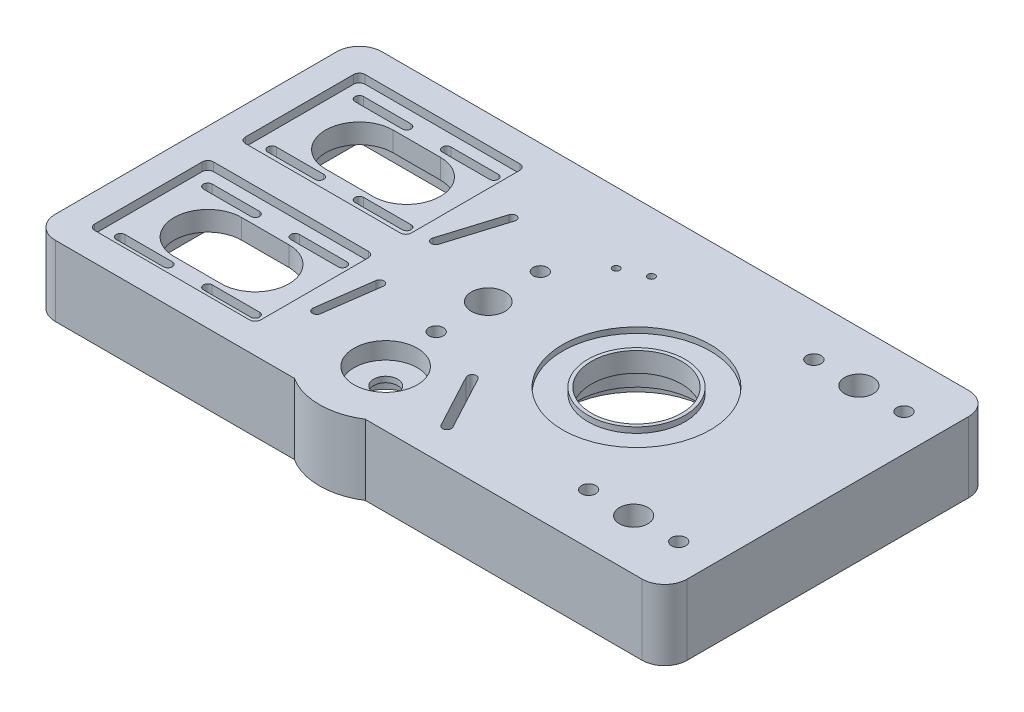
SolidWorks part; units mm, degrees
ref_plane "Front Plane" through (0, 0, 0) normal (0, 0, 1) x (1, 0, 0)
ref_plane "Top Plane" through (0, 0, 0) normal (0, 1, 0) x (1, 0, 0)
ref_plane "Right Plane" through (0, 0, 0) normal (1, 0, 0) x (0, 0, -1)
sketch "Sketch1" plane through (0, 0, 0) normal (0, 1, 0) x (1, 0, 0)
  line L1 (-113.431, 55) -> (95, 55)
  line L2 (-118.431, 50) -> (-118.431, -50)
  line L3 (-113.431, -55) -> (95, -55)
  line L4 (100, 50) -> (100, -50)
  arc A0 (95, 55) -> (100, 50) centre (95, 50) cw
  arc A1 (95, -55) -> (100, -50) centre (95, -50) ccw
  arc A2 (-118.431, -50) -> (-113.431, -55) centre (-113.431, -50) ccw
  arc A3 (-118.431, 50) -> (-113.431, 55) centre (-113.431, 50) cw
  point P0 (0, 0)
  point P18 (0, 0)
  dimension "D3" = 5
  dimension "D1" = 208.431
  dimension "D2" = 110
extrude "Boss-Extrude1" add sketch "Sketch1" along normal blind 10
sketch "Sketch6" plane through (0, 0, 0) normal (0, -1, 0) x (1, 0, 0)
  line L0 (0, 0) -> (35, 0) construction
  circle A0 centre (35, 0) radius 30
  dimension "D2" = 60
  dimension "D1" = 35
extrude "Boss-Extrude3" add sketch "Sketch6" along normal blind 10
sketch "Sketch8" plane through (0, 0, 0) normal (0, 0, 1) x (1, 0, 0)
  line L0 (5, -10) -> (-5, 0)
  line L1 (-5, 0) -> (5, 0)
  line L2 (5, 0) -> (5, -10)
  dimension "D1" = 45
sketch "Sketch9" plane through (0, -10, 0) normal (0, -1, 0) x (1, 0, 0)
  arc A0 (5.1043, 2.5) -> (5.1043, -2.5) centre (35, 0) ccw
  circle A1 centre (35, 0) radius 30 construction
  point P6 (5, 0)
  dimension "D1" = 5
sketch "Sketch10" plane through (0, 0, 0) normal (0, -1, 0) x (1, 0, 0)
  line L0 (-5, -2.5) -> (-5, 2.5)
  line L1 (5, 0) -> (-5, 0) construction
  arc A0 (5.1043, 2.5) -> (5.1043, -2.5) centre (35, 0) ccw construction
  arc A1 (5.1043, 2.5) -> (5.1043, -2.5) centre (35, 0) ccw
  point P4 (-5, 0)
  dimension "D1" = 5
ref_axis "Axis2" through (35, -10, 0) along (0, 1, 0)
ref_plane "Plane1" through (35, 0, 0) normal (1, 0, 0) x (0, 0, -1)
sketch "Sketch40" plane through (0, -10, 0) normal (0, -1, 0) x (1, 0, 0)
  circle A0 centre (35, 0) radius 26.25
  dimension "D1" = 52.5
extrude "Cut-Extrude1" cut sketch "Sketch40" against normal blind 5
sketch "Sketch42" plane through (0, -5, 0) normal (0, -1, 0) x (1, 0, 0)
  circle A0 centre (35, 0) radius 21.25
  dimension "D1" = 42.5
extrude "Cut-Extrude2" cut sketch "Sketch42" against normal blind 8
sketch "Sketch43" plane through (0, 3, 0) normal (0, -1, 0) x (1, 0, 0)
  circle A0 centre (35, 0) radius 16
  dimension "D1" = 32
extrude "Cut-Extrude3" cut sketch "Sketch43" against normal through all
sketch "Sketch44" plane through (0, 10, 0) normal (0, 1, 0) x (1, 0, 0)
  circle A0 centre (35, 0) radius 17.25
  circle A1 centre (35, 0) radius 26.25
  dimension "D1" = 34.5
  dimension "D2" = 52.5
extrude "Cut-Extrude4" cut sketch "Sketch44" against normal blind 2
sketch "Sketch45" plane through (0, 10, 0) normal (0, 1, 0) x (1, 0, 0)
  line L0 (95, 55) -> (-113.431, 55) construction
  line L5 (-109.431, 48) -> (-54.431, 48)
  line L6 (-111.431, 46) -> (-111.431, 7.5)
  line L7 (-109.431, 5.5) -> (-54.431, 5.5)
  line L8 (-52.431, 46) -> (-52.431, 7.5)
  line L9 (-109.431, -5.8) -> (-54.431, -5.8)
  line L10 (-111.431, -7.8) -> (-111.431, -46)
  line L11 (-109.431, -48) -> (-54.431, -48)
  line L12 (-52.431, -7.8) -> (-52.431, -46)
  line L13 (-118.431, 50) -> (-118.431, -50) construction
  line L14 (-113.431, -55) -> (95, -55) construction
  line L15 (100, -50) -> (100, 50) construction
  arc A0 (-111.431, -46) -> (-109.431, -48) centre (-109.431, -46) ccw
  arc A1 (-54.431, -48) -> (-52.431, -46) centre (-54.431, -46) ccw
  arc A2 (-54.431, -5.8) -> (-52.431, -7.8) centre (-54.431, -7.8) cw
  arc A3 (-111.431, -7.8) -> (-109.431, -5.8) centre (-109.431, -7.8) cw
  arc A4 (-109.431, 48) -> (-111.431, 46) centre (-109.431, 46) ccw
  arc A5 (-111.431, 7.5) -> (-109.431, 5.5) centre (-109.431, 7.5) ccw
  arc A6 (-54.431, 5.5) -> (-52.431, 7.5) centre (-54.431, 7.5) ccw
  arc A7 (-54.431, 48) -> (-52.431, 46) centre (-54.431, 46) cw
  point P16 (-111.431, -48)
  point P21 (-52.431, -5.8)
  point P24 (-111.431, -5.8)
  point P27 (-111.431, 48)
  point P30 (-111.431, 5.5)
  point P35 (-52.431, 48)
  dimension "D9" = 2
  dimension "D10" = 2
  dimension "D2" = 42.5
  dimension "D3" = 152.431
  dimension "D4" = 42.2
  dimension "D5" = 7
  dimension "D6" = 7
  dimension "D7" = 7
  dimension "D8" = 7
  dimension "D11" = 152.431
extrude "Cut-Extrude5" cut sketch "Sketch45" against normal blind 3
sketch "Sketch47" plane through (0, 7, 0) normal (0, 1, 0) x (1, 0, 0)
  line L1 (-111.431, -7.8) -> (-111.431, -46) construction
  line L2 (-90.331, -26.9) -> (-73.531, -26.9) construction
  line L5 (-105.831, -11.4) -> (-89.031, -11.4) construction
  line L6 (-90.331, -14.9) -> (-73.531, -14.9)
  line L7 (-73.531, -38.9) -> (-90.331, -38.9)
  line L8 (-52.431, -46) -> (-52.431, -7.8) construction
  line L10 (-105.831, -11.4) -> (-74.831, -11.4) construction
  line L11 (-105.831, -11.4) -> (-105.831, -42.4) construction
  line L12 (-105.831, -42.4) -> (-74.831, -42.4) construction
  line L13 (-74.831, -11.4) -> (-74.831, -42.4) construction
  line L14 (-105.831, -11.4) -> (-74.831, -42.4) construction
  line L15 (-105.831, -42.4) -> (-74.831, -11.4) construction
  line L16 (-89.031, -11.4) -> (-58.031, -11.4) construction
  line L17 (-89.031, -11.4) -> (-89.031, -42.4) construction
  line L18 (-89.031, -42.4) -> (-58.031, -42.4) construction
  line L19 (-58.031, -11.4) -> (-58.031, -42.4) construction
  line L20 (-89.031, -11.4) -> (-58.031, -42.4) construction
  line L21 (-89.031, -42.4) -> (-58.031, -11.4) construction
  line L27 (-105.831, -9.85) -> (-89.031, -9.85)
  line L29 (-105.831, -12.95) -> (-89.031, -12.95)
  line L30 (-58.031, -11.4) -> (-74.831, -11.4) construction
  line L31 (-58.031, -12.95) -> (-74.831, -12.95)
  line L32 (-58.031, -9.85) -> (-74.831, -9.85)
  line L33 (-105.831, -42.4) -> (-89.031, -42.4) construction
  line L34 (-105.831, -40.85) -> (-89.031, -40.85)
  line L35 (-105.831, -43.95) -> (-89.031, -43.95)
  line L36 (-58.031, -42.4) -> (-74.831, -42.4) construction
  line L37 (-58.031, -43.95) -> (-74.831, -43.95)
  line L38 (-58.031, -40.85) -> (-74.831, -40.85)
  arc A1 (-73.531, -38.9) -> (-73.531, -14.9) centre (-73.531, -26.9) ccw
  arc A2 (-90.331, -14.9) -> (-90.331, -38.9) centre (-90.331, -26.9) ccw
  arc A15 (-105.831, -9.85) -> (-105.831, -12.95) centre (-105.831, -11.4) ccw
  arc A16 (-89.031, -12.95) -> (-89.031, -9.85) centre (-89.031, -11.4) ccw
  arc A17 (-58.031, -12.95) -> (-58.031, -9.85) centre (-58.031, -11.4) ccw
  arc A18 (-74.831, -9.85) -> (-74.831, -12.95) centre (-74.831, -11.4) ccw
  arc A19 (-105.831, -40.85) -> (-105.831, -43.95) centre (-105.831, -42.4) ccw
  arc A20 (-89.031, -43.95) -> (-89.031, -40.85) centre (-89.031, -42.4) ccw
  arc A21 (-58.031, -43.95) -> (-58.031, -40.85) centre (-58.031, -42.4) ccw
  arc A22 (-74.831, -40.85) -> (-74.831, -43.95) centre (-74.831, -42.4) ccw
  point P12 (-97.431, -11.4)
  point P23 (-66.431, -11.4)
  point P28 (-97.431, -42.4)
  point P33 (-66.431, -42.4)
  dimension "D1" = 21.1
  dimension "D2" = 24
  dimension "D4" = 24
  dimension "D5" = 31
  dimension "D7" = 3.1
  dimension "D8" = 3.1
  dimension "D9" = 3.1
  dimension "D10" = 3.1
  dimension "D3" = 21.1
  dimension "D6" = 31
  dimension "D11" = 31
  dimension "D12" = 31
extrude "Cut-Extrude6" cut sketch "Sketch47" against normal through all
sketch "Sketch48" plane through (0, 7, 0) normal (0, 1, 0) x (1, 0, 0)
  line L0 (-54.431, 48) -> (-109.431, 48) construction
  line L1 (-111.431, 46) -> (-111.431, 7.5) construction
  circle A0 centre (-81.931, 26.75) radius 3.5
  point P4 (-81.931, 48)
  point P7 (-111.431, 26.75)
  dimension "D1" = 7
extrude "Cut-Extrude7" cut sketch "Sketch48" against normal through all
sketch "Sketch49" plane through (0, 10, 0) normal (0, 1, 0) x (1, 0, 0)
  circle A0 centre (-15.9285, -38.1594) radius 11.25
extrude "Cut-Extrude8" cut sketch "Sketch49" against normal blind 6
sketch "Sketch50" plane through (0, 4, 0) normal (0, 1, 0) x (1, 0, 0)
  circle A0 centre (-15.9285, -38.1594) radius 4.25
  dimension "D1" = 8.5
extrude "Cut-Extrude9" cut sketch "Sketch50" against normal through all
sketch "Sketch51" plane through (0, 0, 0) normal (0, -1, 0) x (1, 0, 0)
  circle A0 centre (-15.9285, 38.1594) radius 11.25
  dimension "D1" = 22.5
extrude "Cut-Extrude10" cut sketch "Sketch51" against normal blind 2
sketch "Sketch56" plane through (0, 10, 0) normal (0, 1, 0) x (1, 0, 0)
  line L0 (90, 40) -> (58, 40) construction
  line L1 (95, 55) -> (-113.431, 55) construction
  line L2 (100, -50) -> (100, 50) construction
  circle A0 centre (74, 40) radius 5.05
  circle A1 centre (58, 40) radius 2.55
  circle A2 centre (90, 40) radius 2.55
  point P5 (74, 40)
  dimension "D1" = 10.1
  dimension "D3" = 5.1
  dimension "D4" = 5.1
  dimension "D2" = 32
  dimension "D5" = 15
  dimension "D6" = 10
extrude "Cut-Extrude13" cut sketch "Sketch56" against normal through all
ref_axis "Axis4" through (74, 0, -40) along (0, 1, 0)
sketch "Sketch54" plane through (0, 10, 0) normal (0, 1, 0) x (1, 0, 0)
  line L0 (-17.6515, -18.5) -> (-17.6515, 18.5) construction
  circle A0 centre (-17.6515, 0) radius 6
  circle A1 centre (-17.6515, 18.5) radius 2.55
  circle A2 centre (-17.6515, -18.5) radius 2.55
  point P5 (-17.6515, 0)
  point P6 (-17.6515, 0)
  dimension "D1" = 12
  dimension "D3" = 5.1
  dimension "D4" = 5.1
  dimension "D2" = 37
  dimension "D5" = 100
extrude "Cut-Extrude12" cut sketch "Sketch54" against normal blind 10
sketch "Sketch55" plane through (0, 10, 0) normal (0, 1, 0) x (1, 0, 0)
  line L0 (90, -40) -> (58, -40) construction
  line L1 (-113.431, -55) -> (95, -55) construction
  line L2 (100, -50) -> (100, 50) construction
  circle A0 centre (74, -40) radius 5.05
  circle A1 centre (58, -40) radius 2.55
  circle A2 centre (90, -40) radius 2.55
  point P5 (74, -40)
  dimension "D1" = 10.1
  dimension "D3" = 5.1
  dimension "D4" = 5.1
  dimension "D2" = 32
  dimension "D5" = 15
  dimension "D6" = 10
extrude "Cut-Extrude14" cut sketch "Sketch55" against normal through all
sketch "Sketch61" plane through (0, 0, 0) normal (0, -1, 0) x (1, 0, 0)
  line L1 (-22.3211, 18.7547) -> (-20.2069, 14.5834)
  line L2 (-20.2069, 14.5834) -> (-15.5373, 14.3286)
  line L3 (-15.5373, 14.3286) -> (-12.9819, 18.2453)
  line L4 (-12.9819, 18.2453) -> (-15.0961, 22.4166)
  line L5 (-15.0961, 22.4166) -> (-19.7657, 22.6714)
  line L6 (-19.7657, 22.6714) -> (-22.3211, 18.7547)
  line L7 (-19.8779, -22.6126) -> (-15.2031, -22.4844)
  line L8 (-15.2031, -22.4844) -> (-12.9767, -18.3718)
  line L9 (-12.9767, -18.3718) -> (-15.4252, -14.3874)
  line L10 (-15.4252, -14.3874) -> (-20.0999, -14.5156)
  line L11 (-20.0999, -14.5156) -> (-22.3263, -18.6282)
  line L12 (-22.3263, -18.6282) -> (-19.8779, -22.6126)
  circle A0 centre (-17.6515, 18.5) radius 4.05 construction
  circle A1 centre (-17.6515, -18.5) radius 4.05 construction
  dimension "D1" = 8.1
  dimension "D2" = 8.1
extrude "Cut-Extrude17" cut sketch "Sketch61" against normal blind 3
ref_axis "Axis5" through (74, 0, 40) along (0, 1, 0)
ref_axis "Axis6" through (-17.6515, 0, 0) along (0, 1, 0)
sketch "Sketch66" plane through (0, 0, 0) normal (0, -1, 0) x (1, 0, 0)
  line L4 (-26.2904, 51) -> (-113.431, 51)
  line L8 (-113.431, -51) -> (95, -51)
  line L9 (96, -50) -> (96, 50)
  line L10 (95, 51) -> (-113.431, 51)
  line L11 (-114.431, 50) -> (-114.431, -50)
  line L12 (-113.431, -51) -> (95, -51)
  line L13 (96, -50) -> (96, 50)
  line L14 (95, 51) -> (-5.5666, 51)
  line L15 (-114.431, 50) -> (-114.431, -50)
  arc A4 (-5.5666, 51) -> (-26.2904, 51) centre (-15.9285, 38.1594) ccw
  arc A8 (95, -51) -> (96, -50) centre (95, -50) ccw
  arc A9 (96, 50) -> (95, 51) centre (95, 50) ccw
  arc A10 (-113.431, 51) -> (-114.431, 50) centre (-113.431, 50) ccw
  arc A11 (-114.431, -50) -> (-113.431, -51) centre (-113.431, -50) ccw
  arc A12 (95, -51) -> (96, -50) centre (95, -50) ccw
  arc A13 (96, 50) -> (95, 51) centre (95, 50) ccw
  arc A14 (-113.431, 51) -> (-114.431, 50) centre (-113.431, 50) ccw
  arc A15 (-114.431, -50) -> (-113.431, -51) centre (-113.431, -50) ccw
  dimension "D2" = 33
  dimension "D1" = 4
extrude "Extrude-Thin4" add sketch "Sketch66" along normal blind 15 and the other way blind 10 thin thin type one direction wall 7
fillet "Fillet2" radius 20 2 edges at (-5.5666, -7.5, 51) (-26.2904, -7.5, 51)
sketch "Sketch70" plane through (0, 0, 0) normal (0, 0, 1) x (1, 0, 0)
  line L0 (62.8394, -8.3805) -> (96.3572, -8.3805)
rib "Rib4" sketch "Sketch70" sketch "Sketch70" thickness 5 extrusion direction parallel to sketch draft on no parameters "D1"=5
ref_axis "Axis7" through (35, 10, 0) along (0, -1, 0)
ref_plane "Plane2" through (35, 0, 0) normal (1, 0, 0) x (0, 0, -1)
sketch "Sketch71" plane through (35, 0, 0) normal (1, 0, 0) x (0, 0, -1)
  line L0 (27.6002, -9.821) -> (51.9246, -9.821)
rib "Rib5" sketch "Sketch71" sketch "Sketch71" thickness 5 extrusion direction parallel to sketch draft on no parameters "D1"=5
sketch "Sketch72" plane through (35, 0, 0) normal (1, 0, 0) x (0, 0, -1)
  line L0 (-28.0959, -9.864) -> (-52.7518, -9.864)
rib "Rib6" sketch "Sketch72" sketch "Sketch72" thickness 5 extrusion direction parallel to sketch draft on no parameters "D1"=5
sketch "Sketch73" plane through (0, 10, 0) normal (0, 1, 0) x (1, 0, 0)
  circle A0 centre (3.5607, 36.7397) radius 1.25
  circle A1 centre (-5.1555, 32.9611) radius 1.25
extrude "Cut-Extrude18" cut sketch "Sketch73" against normal up to next
sketch "Sketch77" plane through (0, 0, 0) normal (0, -1, 0) x (1, 0, 0)
  line L0 (13.3067, 45.6331) -> (2.9884, 26.3868) construction
  line L1 (14.6728, 44.9007) -> (4.3545, 25.6545)
  line L2 (11.9406, 46.3654) -> (1.6224, 27.1192)
  arc A0 (14.6728, 44.9007) -> (11.9406, 46.3654) centre (13.3067, 45.6331) ccw
  arc A1 (1.6224, 27.1192) -> (4.3545, 25.6545) centre (2.9884, 26.3868) ccw
  point P2 (8.1476, 36.0099)
extrude "Cut-Extrude19" cut sketch "Sketch77" against normal up to next
sketch "Sketch80" plane through (0, 0, 0) normal (0, -1, 0) x (1, 0, 0)
  line L0 (-42.565, 13.7036) -> (-45.2535, 33.2752) construction
  line L1 (-44.1005, 13.4927) -> (-46.7891, 33.0642)
  line L2 (-41.0294, 13.9146) -> (-43.7179, 33.4861)
  arc A0 (-44.1005, 13.4927) -> (-41.0294, 13.9146) centre (-42.565, 13.7036) ccw
  arc A1 (-43.7179, 33.4861) -> (-46.7891, 33.0642) centre (-45.2535, 33.2752) ccw
  point P2 (-43.9092, 23.4894)
extrude "Cut-Extrude20" cut sketch "Sketch80" against normal up to next
mirror "Mirror2" about plane through (0, 0, 0) normal (0, 0, 1) of "Cut-Extrude6"
sketch "Sketch81" plane through (0, 0, 0) normal (0, -1, 0) x (1, 0, 0)
  line L0 (-39.2418, -29.9538) -> (-45.5961, -9.29) construction
  line L1 (-40.7233, -30.4094) -> (-47.0776, -9.7456)
  line L2 (-37.7603, -29.4982) -> (-44.1145, -8.8344)
  arc A0 (-40.7233, -30.4094) -> (-37.7603, -29.4982) centre (-39.2418, -29.9538) ccw
  arc A1 (-44.1145, -8.8344) -> (-47.0776, -9.7456) centre (-45.5961, -9.29) ccw
  point P2 (-42.4189, -19.6219)
extrude "Cut-Extrude21" cut sketch "Sketch81" against normal up to next
sketch "Sketch82" plane through (0, 0, 0) normal (0, -1, 0) x (1, 0, 0)
  line L0 (95, 51) -> (37.5, 51) construction
  line L1 (48, 51) -> (96, 51)
  line L2 (48, 51) -> (48, 27.037)
  line L3 (53, 24) -> (96, 24)
  line L4 (96, 51) -> (96, 24)
  line L5 (96, 2.5) -> (96, 50) construction
  line L6 (96, -50) -> (96, -2.5) construction
  line L7 (96, -24) -> (53, -24)
  line L8 (96, -24) -> (96, -51)
  line L9 (96, -51) -> (48, -51)
  line L10 (48, -27.037) -> (48, -51)
  line L11 (37.5, -51) -> (95, -51) construction
  arc A0 (53, 24) -> (48, 27.037) centre (35, 0) ccw
  arc A1 (48, -27.037) -> (53, -24) centre (35, 0) ccw
extrude "Boss-Extrude4" add sketch "Sketch82" along normal blind 10
sketch "Sketch84" plane through (0, 0, 0) normal (0, 1, 0) x (1, 0, 0)
  circle A0 centre (74, 40) radius 5.05
  circle A1 centre (90, 40) radius 2.55
  circle A2 centre (58, 40) radius 2.55
  circle A3 centre (74, -40) radius 5.05
  circle A4 centre (90, -40) radius 2.55
  circle A5 centre (58, -40) radius 2.55
extrude "Cut-Extrude22" cut sketch "Sketch84" against normal up to next
sketch "Sketch86" plane through (-121.431, 0, 0) normal (-1, 0, 0) x (0, 0, 1)
  line L0 (-20, -6) -> (20, -6) construction
  line L2 (50, 10) -> (-50, 10) construction
  circle A0 centre (-20, -6) radius 2.05
  circle A1 centre (20, -6) radius 2.05
  point P2 (0, -6)
  dimension "D2" = 4.1
  dimension "D3" = 4.1
  dimension "D1" = 40
  dimension "D4" = 16
extrude "Cut-Extrude23" cut sketch "Sketch86" against normal up to next
sketch "Sketch87" plane through (0, 0, 0) normal (0, -1, 0) x (1, 0, 0)
  circle A0 centre (-15.9285, 38.1594) radius 14
  circle A1 centre (-15.9285, 38.1594) radius 11.25
  dimension "D1" = 28
extrude "Boss-Extrude5" add sketch "Sketch87" along normal blind 5
sketch "Sketch88" plane through (0, -10, 0) normal (0, -1, 0) x (1, 0, 0)
  line L0 (48, 36.2159) -> (63.8953, 24)
  line L1 (48, 51) -> (96, 51)
  line L2 (48, 51) -> (48, 36.2159)
  line L3 (63.8953, 24) -> (96, 24)
  line L4 (96, 51) -> (96, 24)
  line L5 (48, -36.2389) -> (64.863, -24)
  line L6 (48, -51) -> (96, -51)
  line L7 (48, -51) -> (48, -36.2389)
  line L8 (64.863, -24) -> (96, -24)
  line L9 (96, -51) -> (96, -24)
extrude "Boss-Extrude6" add sketch "Sketch88" along normal blind 5
sketch "Sketch89" plane through (0, -10, 0) normal (0, 1, 0) x (1, 0, 0)
  circle A0 centre (74, -40) radius 5.05
  circle A1 centre (58, -40) radius 2.55
  circle A2 centre (90, -40) radius 2.55
  circle A3 centre (74, 40) radius 5.05
  circle A4 centre (90, 40) radius 2.55
  circle A5 centre (58, 40) radius 2.55
extrude "Cut-Extrude24" cut sketch "Sketch89" against normal up to next
